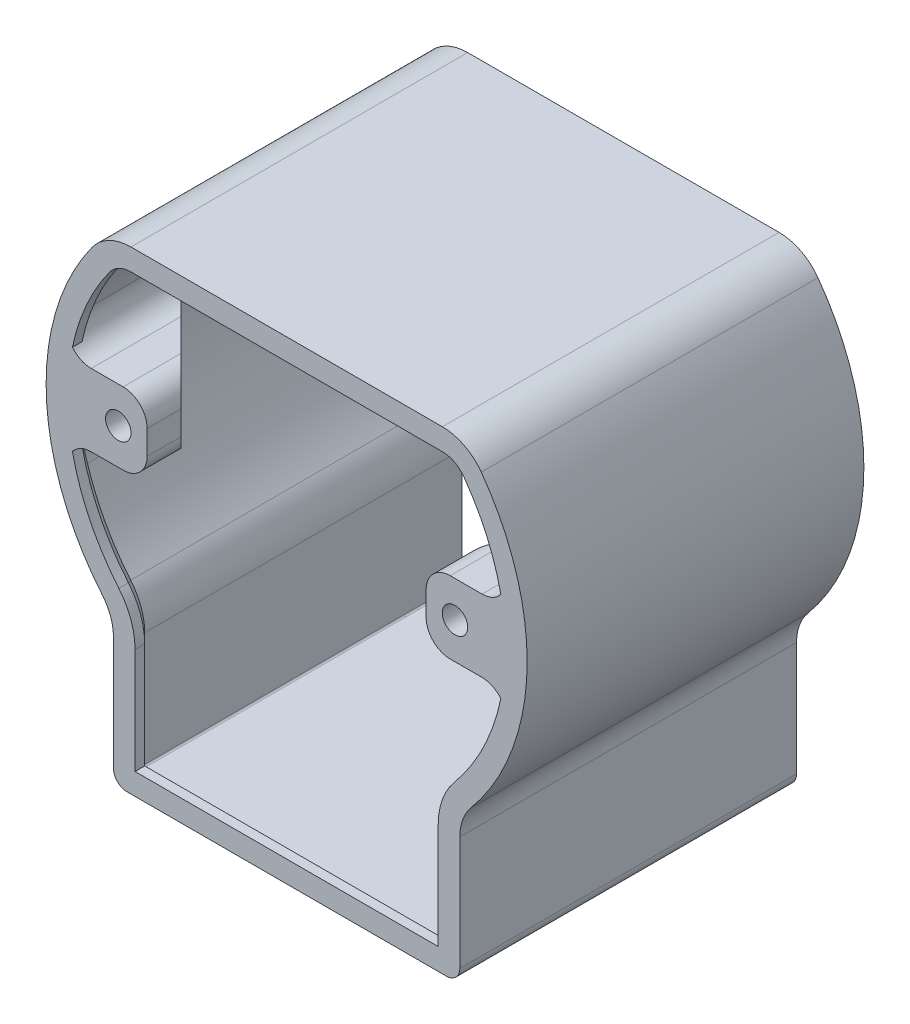
SolidWorks part; units mm, degrees
ref_plane "Ebene vorne" through (0, 0, 0) normal (0, 0, 1) x (1, 0, 0)
ref_plane "Ebene oben" through (0, 0, 0) normal (0, 1, 0) x (1, 0, 0)
ref_plane "Ebene rechts" through (0, 0, 0) normal (1, 0, 0) x (0, 0, -1)
sketch "Skizze1" plane through (0, 0, 0) normal (0, 0, 1) x (1, 0, 0)
  line L0 (0, 15.499) -> (0, -28.3741) construction
  line L1 (0, 33.5) -> (-32.369, 33.5)
  line L2 (0, 33.5) -> (32.369, 33.5)
  line L3 (-36, -38.5227) -> (-36, -62.2)
  line L4 (-33.2, -65) -> (0, -65)
  line L5 (-50, 78.1636) -> (-50, -33.9451) construction
  line L6 (50, 78.1636) -> (50, -33.9451) construction
  line L7 (-50, 0) -> (50, 0) construction
  line L8 (36, -38.5227) -> (36, -62.2)
  line L10 (0, -65) -> (33.2, -65)
  arc A0 (-40.4612, 29.375) -> (-38.3333, -32.1023) centre (0, 0) ccw
  arc A3 (40.4612, 29.375) -> (38.3333, -32.1023) centre (0, 0) cw
  arc A8 (32.369, 33.5) -> (40.4612, 29.375) centre (32.369, 23.5) cw
  arc A9 (-32.369, 33.5) -> (-40.4612, 29.375) centre (-32.369, 23.5) ccw
  arc A10 (38.3333, -32.1023) -> (36, -38.5227) centre (46, -38.5227) ccw
  arc A11 (-38.3333, -32.1023) -> (-36, -38.5227) centre (-46, -38.5227) cw
  arc A12 (36, -62.2) -> (33.2, -65) centre (33.2, -62.2) cw
  arc A13 (-36, -62.2) -> (-33.2, -65) centre (-33.2, -62.2) ccw
  point P18 (0, 0)
  point P34 (36, -65)
  point P37 (-36, -65)
  dimension "D1" = 72
  dimension "D4" = 10
  dimension "D2" = 10
  dimension "D7" = 2.8
  dimension "D3" = 65
  dimension "D5" = 33.5
  dimension "D6" = 100
extrude "Linear-Austragen-Dünn1" add sketch "Skizze1" along normal blind 70 thin thin type one direction reverse wall 2.49
sketch "Skizze16" plane through (0, 0, 70) normal (0, 0, 1) x (1, 0, 0)
  line L0 (33.51, -62.2) -> (33.51, -38.5227) construction
  line L1 (32.369, 31.01) -> (-32.369, 31.01) construction
  line L2 (-33.51, -38.5227) -> (-33.51, -62.2) construction
  line L3 (-33.2, -62.51) -> (33.2, -62.51) construction
  line L4 (33.51, -62.2) -> (33.51, -38.5227)
  line L5 (32.369, 31.01) -> (-32.369, 31.01)
  line L6 (-33.51, -38.5227) -> (-33.51, -62.2)
  line L7 (-33.2, -62.51) -> (33.2, -62.51)
  arc A0 (33.2, -62.51) -> (33.51, -62.2) centre (33.2, -62.2) ccw construction
  arc A1 (36.4243, -30.5036) -> (33.51, -38.5227) centre (46, -38.5227) ccw construction
  arc A2 (36.4243, -30.5036) -> (38.4462, 27.9121) centre (0, 0) ccw construction
  arc A3 (38.4462, 27.9121) -> (32.369, 31.01) centre (32.369, 23.5) ccw construction
  arc A4 (-32.369, 31.01) -> (-38.4462, 27.9121) centre (-32.369, 23.5) ccw construction
  arc A5 (-38.4462, 27.9121) -> (-36.4243, -30.5036) centre (0, 0) ccw construction
  arc A6 (-33.51, -38.5227) -> (-36.4243, -30.5036) centre (-46, -38.5227) ccw construction
  arc A7 (-33.51, -62.2) -> (-33.2, -62.51) centre (-33.2, -62.2) ccw construction
  arc A8 (33.2, -62.51) -> (33.51, -62.2) centre (33.2, -62.2) ccw
  arc A9 (36.4243, -30.5036) -> (33.51, -38.5227) centre (46, -38.5227) ccw
  arc A10 (36.4243, -30.5036) -> (38.4462, 27.9121) centre (0, 0) ccw
  arc A11 (38.4462, 27.9121) -> (32.369, 31.01) centre (32.369, 23.5) ccw
  arc A12 (-32.369, 31.01) -> (-38.4462, 27.9121) centre (-32.369, 23.5) ccw
  arc A13 (-38.4462, 27.9121) -> (-36.4243, -30.5036) centre (0, 0) ccw
  arc A14 (-33.51, -38.5227) -> (-36.4243, -30.5036) centre (-46, -38.5227) ccw
  arc A15 (-33.51, -62.2) -> (-33.2, -62.51) centre (-33.2, -62.2) ccw
sketch "Skizze17" plane through (0, 0, 0) normal (1, 0, 0) x (0, 0, -1)
  line L0 (-70, 31.01) -> (-70, 29.01)
  line L1 (-70, 27.9121) -> (-70, -30.5036) construction
  line L3 (-70, 31.01) -> (0, 31.01) construction
  line L4 (-66, 31.01) -> (-70, 31.01)
  line L5 (-70, 29.01) -> (-68, 29.01)
  line L6 (-68, 29.01) -> (-66, 31.01)
  line L7 (-70, 27.9121) -> (-70, -30.5036) construction
  line L8 (-70, 31.01) -> (-70, -62.51) construction
  line L9 (-70, -62.2) -> (-70, -62.51) construction
  line L10 (-70, -62.2) -> (-70, -65) construction
  line L11 (-70, -15.75) -> (0, -15.75) construction
  line L12 (0, -30.5036) -> (0, 27.9121) construction
  line L13 (-68, -60.51) -> (-66, -62.51)
  line L14 (-70, -60.51) -> (-68, -60.51)
  line L15 (-66, -62.51) -> (-70, -62.51)
  line L16 (-70, -62.51) -> (-70, -60.51)
  dimension "D1" = 45
  dimension "D2" = 2
  dimension "D3" = 2
sweep "Austragung2" add profiles "Skizze17" path "Skizze16"
sketch "Skizze6" plane through (0, 0, 0) normal (1, 0, 0) x (0, 0, -1)
  line L0 (-70, 29.375) -> (-70, -32.1023) construction
  line L1 (-70, 7.5) -> (-45, 7.5)
  line L2 (-70, 7.5) -> (-70, -7.5)
  line L3 (-70, -7.5) -> (-45, -7.5)
  line L4 (-45, 7.5) -> (-45, -7.5)
  line L5 (55, 0) -> (-55, 0) construction
  line L6 (0, -32.1023) -> (0, 29.375) construction
  line L7 (0, 7.5) -> (-25, 7.5)
  line L8 (0, 7.5) -> (0, -7.5)
  line L9 (0, -7.5) -> (-25, -7.5)
  line L10 (-25, 7.5) -> (-25, -7.5)
  point P6 (-70, 0)
  dimension "D1" = 15
  dimension "D2" = 25
  dimension "D3" = 25
extrude "Aufsatz-Linear austragen3" add sketch "Skizze6" along normal up to next from offset 29
mirror "Spiegeln1" about plane through (0, 0, 0) normal (1, 0, 0) of "Aufsatz-Linear austragen3"
chamfer "Fase1" distance 18 angle 45 4 edges at (29, 0, 45) (-29, 0, 45) (29, 0, 25) (-29, 0, 25)
sketch "Skizze2" plane through (0, 0, 70) normal (0, 0, -1) x (-1, 0, 0)
  line L0 (-32.369, 33.5) -> (32.369, 33.5) construction
  line L1 (36, -38.5227) -> (36, -62.2) construction
  line L2 (33.2, -65) -> (-33.2, -65) construction
  line L3 (-36, -62.2) -> (-36, -38.5227) construction
  line L4 (-32.369, 33.5) -> (32.369, 33.5)
  line L5 (36, -38.5227) -> (36, -62.2)
  line L6 (33.2, -65) -> (-33.2, -65)
  line L7 (-36, -62.2) -> (-36, -38.5227)
  line L8 (0, 31.01) -> (0, -62.51) construction
  line L9 (-28.75, 28.75) -> (28.75, 28.75)
  line L10 (-28.75, 28.75) -> (-28.75, -28.75)
  line L11 (-28.75, -28.75) -> (28.75, -28.75)
  line L12 (28.75, 28.75) -> (28.75, -28.75)
  line L13 (-28.75, 28.75) -> (28.75, -28.75) construction
  line L14 (-28.75, -28.75) -> (28.75, 28.75) construction
  line L15 (-28.75, -28.75) -> (28.75, -28.75)
  line L16 (-28.75, -28.75) -> (-28.75, -58.75)
  line L17 (-28.75, -58.75) -> (28.75, -58.75)
  line L18 (28.75, -28.75) -> (28.75, -58.75)
  line L19 (-32.369, 31.01) -> (32.369, 31.01) construction
  line L20 (33.2, -62.51) -> (-33.2, -62.51) construction
  arc A0 (-32.369, 33.5) -> (-40.4612, 29.375) centre (-32.369, 23.5) ccw construction
  arc A1 (40.4612, 29.375) -> (32.369, 33.5) centre (32.369, 23.5) ccw construction
  arc A2 (38.3333, -32.1023) -> (40.4612, 29.375) centre (0, 0) ccw construction
  arc A3 (38.3333, -32.1023) -> (36, -38.5227) centre (46, -38.5227) ccw construction
  arc A4 (33.2, -65) -> (36, -62.2) centre (33.2, -62.2) ccw construction
  arc A5 (-36, -62.2) -> (-33.2, -65) centre (-33.2, -62.2) ccw construction
  arc A6 (-36, -38.5227) -> (-38.3333, -32.1023) centre (-46, -38.5227) ccw construction
  arc A7 (-40.4612, 29.375) -> (-38.3333, -32.1023) centre (0, 0) ccw construction
  arc A8 (-32.369, 33.5) -> (-40.4612, 29.375) centre (-32.369, 23.5) ccw
  arc A9 (40.4612, 29.375) -> (32.369, 33.5) centre (32.369, 23.5) ccw
  arc A10 (38.3333, -32.1023) -> (40.4612, 29.375) centre (0, 0) ccw
  arc A11 (38.3333, -32.1023) -> (36, -38.5227) centre (46, -38.5227) ccw
  arc A12 (33.2, -65) -> (36, -62.2) centre (33.2, -62.2) ccw
  arc A13 (-36, -62.2) -> (-33.2, -65) centre (-33.2, -62.2) ccw
  arc A14 (-36, -38.5227) -> (-38.3333, -32.1023) centre (-46, -38.5227) ccw
  arc A15 (-40.4612, 29.375) -> (-38.3333, -32.1023) centre (0, 0) ccw
  circle A16 centre (-35, 0) radius 2.65
  circle A17 centre (35, 0) radius 2.65
  dimension "D3" = 70
  dimension "D4" = 5.3
  dimension "D1" = 57.5
  dimension "D2" = 30
sketch "Skizze7" plane through (0, 0, 70) normal (0, 0, 1) x (1, 0, 0)
  line L0 (0, 0) -> (0, 33.5) construction
  line L1 (32.369, 33.5) -> (-32.369, 33.5) construction
  circle A0 centre (-35, 0) radius 2.65
  circle A1 centre (35, 0) radius 2.65
  dimension "D1" = 5.3
  dimension "D2" = 70
extrude "Schnitt-Linear austragen3" cut sketch "Skizze7" against normal through all
sketch "Skizze9" plane through (0, 0, 70) normal (0, 0, 1) x (1, 0, 0)
  line L1 (-39.6188, 0) -> (-37.3094, -4)
  line L2 (-37.3094, -4) -> (-32.6906, -4)
  line L3 (-32.6906, -4) -> (-30.3812, 0)
  line L4 (-30.3812, 0) -> (-32.6906, 4)
  line L5 (-32.6906, 4) -> (-37.3094, 4)
  line L6 (-37.3094, 4) -> (-39.6188, 0)
  line L7 (30.3812, 0) -> (32.6906, -4)
  line L8 (32.6906, -4) -> (37.3094, -4)
  line L9 (37.3094, -4) -> (39.6188, 0)
  line L10 (39.6188, 0) -> (37.3094, 4)
  line L11 (37.3094, 4) -> (32.6906, 4)
  line L12 (32.6906, 4) -> (30.3812, 0)
  circle A2 centre (-35, 0) radius 4 construction
  circle A3 centre (35, 0) radius 4 construction
  dimension "D1" = 8
extrude "Schnitt-Linear austragen5" cut sketch "Skizze9" against normal blind 90 from offset 5 offset against normal yes
fillet "Verrundung1" radius 5 16 edges at (-46.9143, 7.5, 55.5429) (-29, 7.5, 66.5) (-29, -7.5, 66.5) (-46.9143, -7.5, 55.5429) (46.9143, -7.5, 55.5429) (29, -7.5, 66.5) (29, 7.5, 66.5) (46.9143, 7.5, 55.5429) (-46.9143, -7.5, 12.4571) (-29, -7.5, 3.5) (-29, 7.5, 3.5) (-46.9143, 7.5, 12.4571) (46.9143, -7.5, 12.4571) (29, -7.5, 3.5) (29, 7.5, 3.5) (46.9143, 7.5, 12.4571)
extrude "Aufsatz-Linear austragen5" add sketch "Skizze17<3>" against normal up to next and the other way up to next contours L13 L15 L16 L14
sketch "Skizze17<3>" plane through (0, 0, 0) normal (1, 0, 0) x (0, 0, -1) same geometry as "Skizze17"
